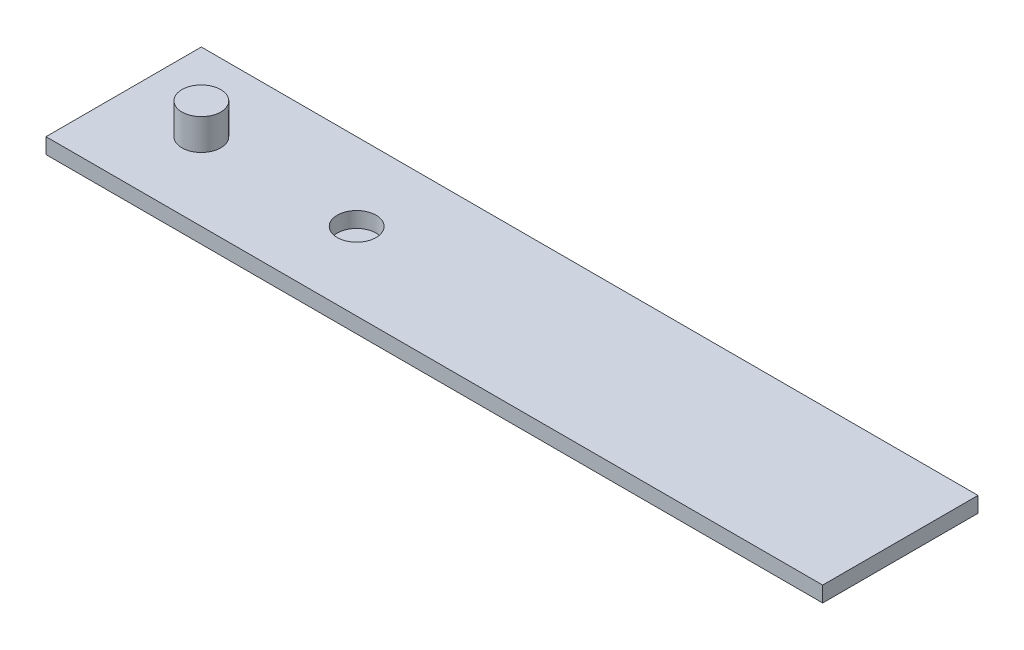
SolidWorks part; units mm, degrees
ref_plane "Front" through (0, 0, 0) normal (0, 0, 1) x (1, 0, 0)
ref_plane "Top" through (0, 0, 0) normal (0, 1, 0) x (1, 0, 0)
ref_plane "Right" through (0, 0, 0) normal (1, 0, 0) x (0, 0, -1)
sketch "Sketch2" plane through (0, 0, 0) normal (0, 1, 0) x (1, 0, 0)
  line L0 (0, 12.7) -> (127, 12.7) construction
  line L1 (0, 0) -> (127, 0)
  line L2 (0, 0) -> (0, 25.4)
  line L3 (0, 25.4) -> (127, 25.4)
  line L4 (127, 0) -> (127, 25.4)
  circle A0 centre (12.7, 12.7) radius 3.175
  circle A1 centre (38.1, 12.7) radius 3.175
  dimension "D3" = 6.35
  dimension "D4" = 25.4
  dimension "D1" = 127
  dimension "D2" = 25.4
  dimension "D5" = 12.7
extrude "Boss-Extrude1" add sketch "Sketch2" along normal blind 2.54
extrude "Boss-Extrude2" add sketch "Sketch2<2>" along normal blind 7.62 contours A0 L0 | L0 A0 region at (12.7, 0, -11.3525) region at (12.7, 0, -14.0475)
sketch "Sketch2<2>" plane through (0, 0, 0) normal (0, 1, 0) x (1, 0, 0) same geometry as "Sketch2"
extrude "Boss-Extrude3" add sketch "Sketch2<3>" against normal blind 2.54 separate body contours L0 A1 | A1 L0 region at (38.1, 0, -11.3525) region at (38.1, 0, -14.0475)
sketch "Sketch2<3>" plane through (0, 0, 0) normal (0, 1, 0) x (1, 0, 0) same geometry as "Sketch2"
